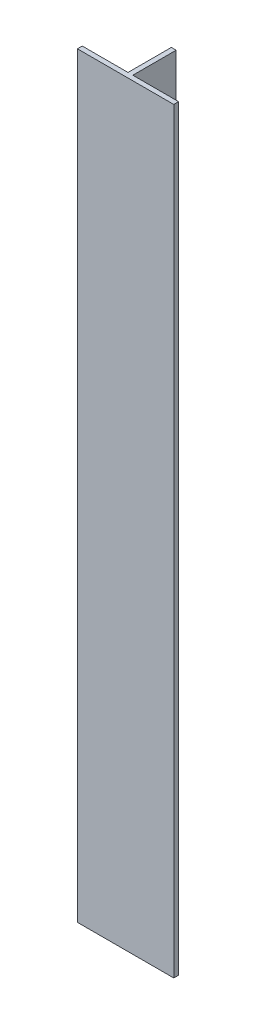
SolidWorks part; units mm, degrees
ref_plane "Front Plane" through (0, 0, 0) normal (0, 0, 1) x (1, 0, 0)
ref_plane "Top Plane" through (0, 0, 0) normal (0, 1, 0) x (1, 0, 0)
ref_plane "Right Plane" through (0, 0, 0) normal (1, 0, 0) x (0, 0, -1)
sketch "Sketch1" plane through (0, 0, 0) normal (0, 1, 0) x (1, 0, 0)
  line L0 (0, 5.3611) -> (0, 23.3611)
  line L1 (0, 23.3611) -> (2, 23.3611)
  line L2 (2, 23.3611) -> (2, 5.3611)
  line L3 (2, 5.3611) -> (21, 5.3611)
  line L4 (21, 5.3611) -> (21, 3.3611)
  line L5 (21, 3.3611) -> (-19, 3.3611)
  line L6 (-19, 3.3611) -> (-19, 5.3611)
  line L7 (-19, 5.3611) -> (0, 5.3611)
extrude "Boss-Extrude1" add sketch "Sketch1" along normal up to surface (314 mm away)
